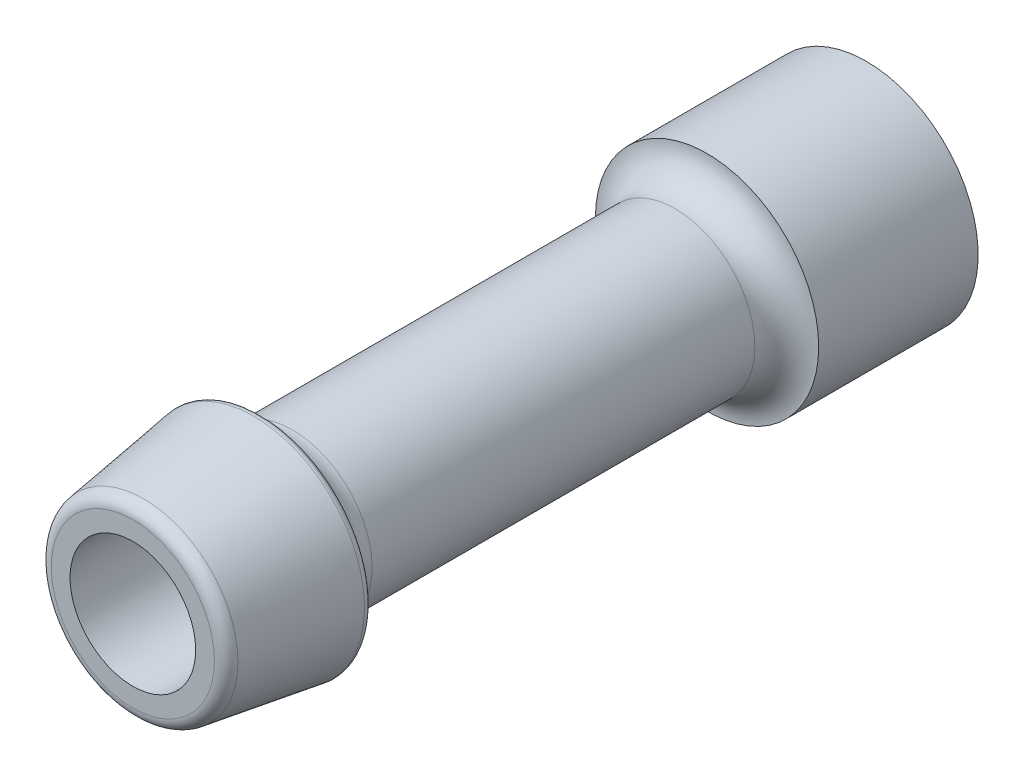
SolidWorks part; units mm, degrees
material "Custom Plastic"
ref_plane "X-Y Datum" through (0, 0, 0) normal (0, 0, 1) x (1, 0, 0)
ref_plane "X-Z Datum" through (0, 0, 0) normal (0, 1, 0) x (1, 0, 0)
ref_plane "Y-Z Datum" through (0, 0, 0) normal (1, 0, 0) x (0, 0, -1)
sketch "Sketch1" plane through (0, 0, 0) normal (0, 0, 1) x (1, 0, 0)
  circle A0 centre (0, 0) radius 4.445
  dimension "D1" = 8.89
extrude "Boss-Extrude1" add sketch "Sketch1" along normal blind 29.21
sketch3d "3DSketch1"
  line L0 (0, 0, 29.21) -> (0, 0, 0)
  line L1 (0, 0, 29.21) -> (0, 0, 0) construction
sketch "Sketch2" plane through (0, 0, 29.21) normal (0, 0, 1) x (1, 0, 0)
  circle A0 centre (0, 0) radius 2.5
  dimension "D1" = 5
sweep "Cut-Sweep1" cut profiles "Sketch2" path "3DSketch1"
sketch "Sketch3" plane through (0, 0, 29.21) normal (0, 0, 1) x (1, 0, 0)
  circle A0 centre (0, 0) radius 3.175
  circle A1 centre (0, 0) radius 6.35
  dimension "D1" = 12.7
  dimension "D2" = 6.35
extrude "Cut-Extrude1" cut sketch "Sketch3" against normal blind 17.78 from offset 5.08 offset against normal yes
fillet "Fillet1" radius 1.27 1 edges at (3.175, 0, 6.35)
fillet "Fillet2" radius 1.27 1 edges at (3.175, 0, 24.13)
chamfer "Chamfer1" distance 5.08 angle 8.5 1 edges at (4.445, 0, 29.21) first distance on face at (4.445, 0, 24.13)
fillet "Fillet3" radius 0.254 1 edges at (4.445, 0, 24.13)
fillet "Fillet4" radius 0.508 1 edges at (3.6858, 0, 29.21)
